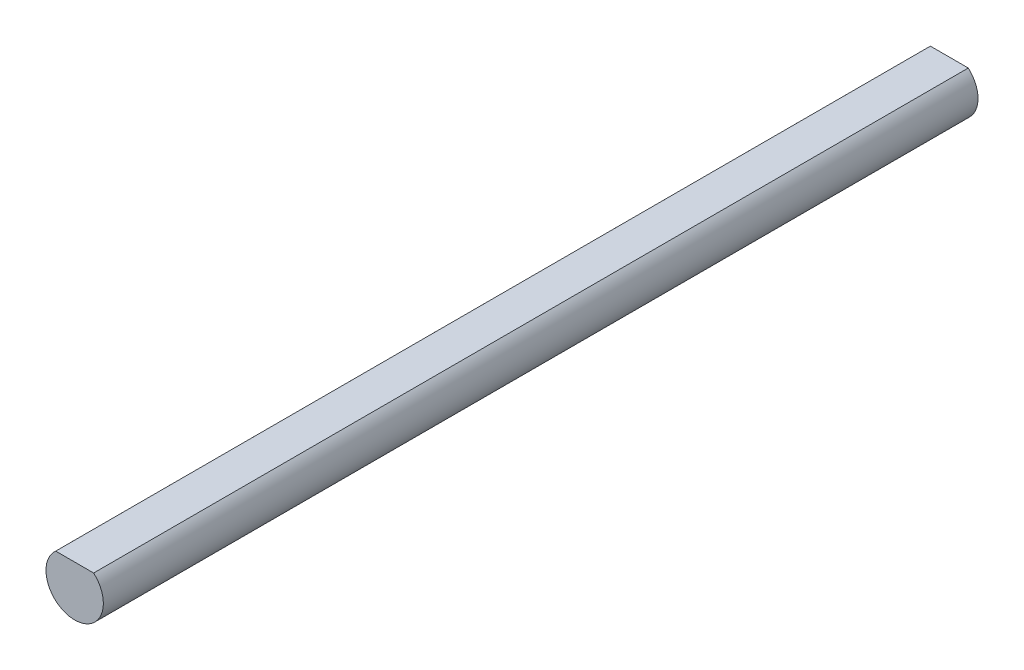
SolidWorks part; units mm, degrees
material "Stainless Steel (ferritic)"
ref_plane "Front Plane" through (0, 0, 0) normal (0, 0, 1) x (1, 0, 0)
ref_plane "Top Plane" through (0, 0, 0) normal (0, 1, 0) x (1, 0, 0)
ref_plane "Right Plane" through (0, 0, 0) normal (1, 0, 0) x (0, 0, -1)
sketch "Sketch1" plane through (0, 0, 0) normal (0, 0, 1) x (1, 0, 0)
  circle A0 centre (0, 0) radius 4
extrude "Boss-Extrude1" add sketch "Sketch1" along normal blind 61 and the other way blind 61
sketch "Sketch2" plane through (0, 0, 61) normal (0, 0, 1) x (1, 0, 0)
  line L0 (-2.6458, 3) -> (2.6458, 3)
  circle A1 centre (0, 0) radius 4 construction
  arc A2 (-2.6458, 3) -> (2.6458, 3) centre (0, 0) cw
  dimension "D1" = 3
extrude "Cut-Extrude1" cut sketch "Sketch2" against normal blind 122
